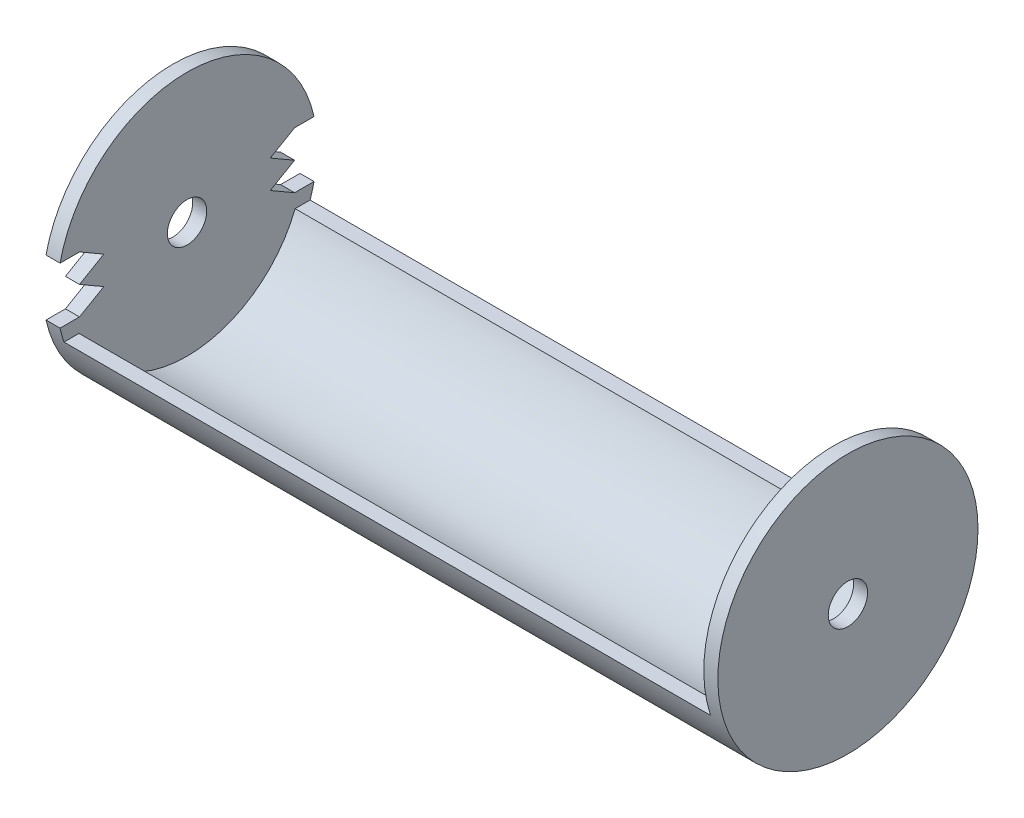
SolidWorks part; units mm, degrees
material "CMR DEFAULT - CHANGE MATERIAL"
ref_plane "XY PLANE - TOP" through (0, 0, 0) normal (0, 0, 1) x (1, 0, 0)
ref_plane "XZ PLANE - SIDE" through (0, 0, 0) normal (0, 1, 0) x (1, 0, 0)
ref_plane "YZ PLANE - FRONT" through (0, 0, 0) normal (1, 0, 0) x (0, 0, -1)
sketch "Sketch1" plane through (0, 0, 0) normal (1, 0, 0) x (0, 0, -1)
  circle A0 centre (0, 0) radius 58.7375
  circle A1 centre (0, 0) radius 8.89
  dimension "D1" = 117.475
  dimension "D2" = 17.78
extrude "Boss-Extrude1" add sketch "Sketch1" along normal mid plane 304.8
sketch "Sketch2" plane through (0, 0, 0) normal (0, 0, 1) x (1, 0, 0)
  line L0 (152.4, 58.7375) -> (-152.4, 58.7375) construction
  line L1 (-146.05, 58.7375) -> (146.05, 58.7375)
  line L2 (-146.05, 58.7375) -> (-146.05, -19.05)
  line L3 (-146.05, -19.05) -> (146.05, -19.05)
  line L4 (146.05, 58.7375) -> (146.05, -19.05)
  line L5 (0, -19.05) -> (0, 58.7375) construction
  line L6 (-146.05, 19.8438) -> (146.05, 19.8438) construction
  line L7 (0, -55) -> (0, 55) construction
  line L8 (-152.4, 58.7375) -> (-152.4, -58.7375) construction
  line L10 (88.5065, 0) -> (-88.5065, 0) construction
  point P284 (0, 19.8438)
  dimension "D1" = 6.35
  dimension "D2" = 19.05
extrude "Cut-Extrude1" cut sketch "Sketch2" against normal through all both and the other way through all
shell "Shell1" thickness 6.35 removed face at (0, -19.05, 0)
sketch "Sketch3" plane through (-152.4, 0, 0) normal (-1, 0, 0) x (0, 0, 1)
  line L0 (-48.5775, 12.7) -> (-37.579, 6.35)
  line L1 (-37.579, 6.35) -> (-48.5775, 0)
  line L2 (-48.5775, 0) -> (-37.579, -6.35)
  line L3 (-37.579, -6.35) -> (-48.5775, -12.7)
  line L4 (-48.5775, -12.7) -> (-58.7375, -12.7)
  line L5 (-48.5775, 12.7) -> (-58.7375, 12.7)
  line L6 (-58.7375, 12.7) -> (-58.7375, -12.7)
  line L7 (58.7375, 0) -> (-58.7375, 0) construction
  line L8 (0, 58.7375) -> (0, -58.7375) construction
  line L9 (48.5775, 12.7) -> (58.7375, 12.7)
  line L10 (48.5775, 12.7) -> (37.579, 6.35)
  line L11 (37.579, 6.35) -> (48.5775, 0)
  line L12 (48.5775, 0) -> (37.579, -6.35)
  line L13 (37.579, -6.35) -> (48.5775, -12.7)
  line L14 (48.5775, -12.7) -> (58.7375, -12.7)
  line L15 (58.7375, 12.7) -> (58.7375, -12.7)
  circle A0 centre (0, 0) radius 58.7375 construction
  point P5 (-58.7375, 0)
  dimension "D1" = 12.7
  dimension "D2" = 12.7
  dimension "D3" = 10.16
extrude "Cut-Extrude2" cut sketch "Sketch3" against normal blind 12.7
